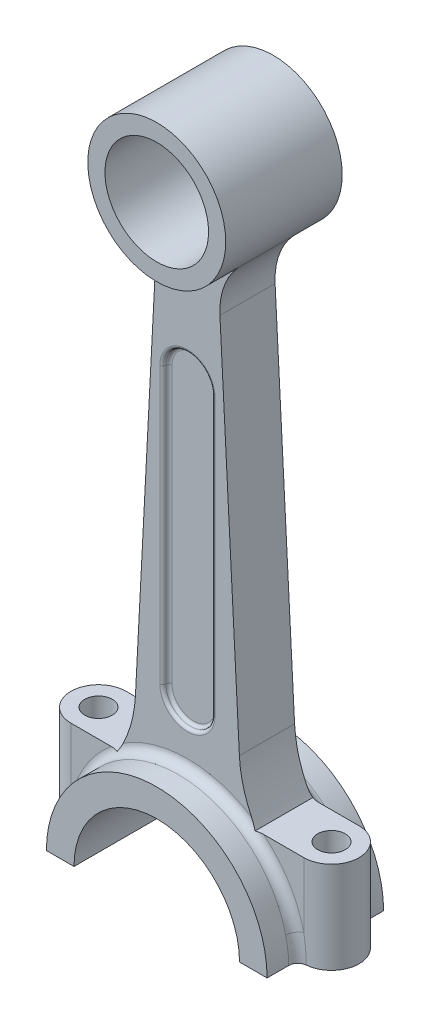
SolidWorks part; units mm, degrees
ref_plane "Piano frontale" through (0, 0, 0) normal (0, 0, 1) x (1, 0, 0)
ref_plane "Piano superiore" through (0, 0, 0) normal (0, 1, 0) x (1, 0, 0)
ref_plane "Piano destro" through (0, 0, 0) normal (1, 0, 0) x (0, 0, -1)
sketch "Schizzo1" plane through (0, 0, 0) normal (0, 0, 1) x (1, 0, 0)
  line L0 (0, 0) -> (0, -201.2) construction
  line L1 (-10, -20.1556) -> (-17.8497, -169.9368)
  line L2 (10, -20.1556) -> (17.8497, -169.9368)
  line L3 (36, -201.2) -> (27, -201.2)
  line L4 (0, -201.2) -> (-36, -201.2)
  circle A0 centre (0, 0) radius 22.5
  circle A1 centre (0, 0) radius 16.9
  arc A2 (27, -201.2) -> (-27, -201.2) centre (0, -201.2) ccw
  arc A3 (36, -201.2) -> (-36, -201.2) centre (0, -201.2) ccw
  dimension "D1" = 45
  dimension "D2" = 33.8
  dimension "D3" = 54
  dimension "D4" = 72
  dimension "D5" = 201.2
  dimension "D6" = 20
  dimension "D7" = 6
extrude "Estrusione-Estrusione1" add sketch "Schizzo1" along normal mid plane 38 contours A3 A2 | A1 A0 | L0 A3 L4 A2 region at (-4.9903, -21.2865, 0) region at (20.1899, -181.0101, 0) region at (-20.1899, -181.0101, 0)
extrude "Estrusione-Estrusione2" add sketch "Schizzo1<4>" along normal mid plane 18 contours A0 L0 A3 L2 | L0 A0 L1 A3 region at (7.1843, -100.8455, 0) region at (-7.1843, -100.8455, 0)
sketch "Schizzo1<4>" plane through (0, 0, 0) normal (0, 0, 1) x (1, 0, 0) same geometry as "Schizzo1"
sketch "Schizzo2" plane through (0, 0, -9) normal (0, 0, -1) x (-1, 0, 0)
  line L0 (0, 0) -> (0, -201.2) construction
  line L1 (0, -145.6) -> (0, -55.6) construction
  line L2 (-8, -145.6) -> (-8, -55.6)
  line L3 (8, -145.6) -> (8, -55.6)
  arc A0 (-8, -145.6) -> (8, -145.6) centre (0, -145.6) ccw
  arc A1 (8, -55.6) -> (-8, -55.6) centre (0, -55.6) ccw
  point P6 (0, -100.6)
  dimension "D2" = 8
  dimension "D1" = 90
extrude "Taglio-Estrusione1" cut sketch "Schizzo2" against normal mid plane 4
mirror "Specchia1" about plane through (0, 0, 0) normal (0, 0, 1) of "Taglio-Estrusione1"
fillet "Raccordo5" radius 1 16 edges at (0, -153.6, 9) (8, -100.6, 9) (0, -47.6, 9) (0, -47.6, -9) (8, -100.6, -9) (0, -153.6, -9) (0, -153.6, -7) (8, -100.6, -7) (0, -47.6, -7) (-8, -100.6, 7) (0, -47.6, 7) (8, -100.6, 7) (0, -153.6, 7) (-8, -100.6, 9) (-8, -100.6, -9) (-8, -100.6, -7)
fillet "Raccordo6" radius 40 2 edges at (-17.8497, -169.9368, 0) (17.8497, -169.9368, 0)
fillet "Raccordo7" radius 22.5 2 edges at (-10, -20.1556, 0) (10, -20.1556, 0)
ref_plane "Piano1" through (0, -171.2, 0) normal (0, -1, 0) x (-1, 0, 0)
sketch "Schizzo3" plane through (0, -171.2, 0) normal (0, -1, 0) x (-1, 0, 0)
  line L0 (38, 0) -> (-38, 0) construction
  line L1 (38, -9) -> (-38, -9)
  line L2 (38, 9) -> (-38, 9)
  arc A0 (38, -9) -> (38, 9) centre (38, 0) ccw
  arc A1 (-38, 9) -> (-38, -9) centre (-38, 0) ccw
  point P2 (0, 0)
  dimension "D2" = 9
  dimension "D1" = 76
extrude "Estrusione-Estrusione3" add sketch "Schizzo3" along normal up to surface (30 mm away) up to face at (31.5, -201.2, 0)
sketch "Schizzo4" plane through (0, 0, -9) normal (0, 0, -1) x (-1, 0, 0)
  line L1 (-27, -201.2) -> (27, -201.2)
  line L2 (-27, -201.2) -> (27, -201.2)
  arc A1 (27, -201.2) -> (-27, -201.2) centre (0, -201.2) ccw
  arc A2 (27, -201.2) -> (-27, -201.2) centre (0, -201.2) ccw
  dimension "D1" = 0
extrude "Taglio-Estrusione2" cut sketch "Schizzo4" against normal through all
sketch "Schizzo5" plane through (0, -171.2, 0) normal (0, 1, 0) x (1, 0, 0)
  circle A0 centre (-38, 0) radius 4.5
  circle A1 centre (38, 0) radius 4.5
  dimension "D1" = 9
  dimension "D2" = 9
extrude "Taglio-Estrusione3" cut sketch "Schizzo5" against normal through all
fillet "Raccordo8" radius 3 2 edges at (0, -165.2, -9) (0, -165.2, 9)
